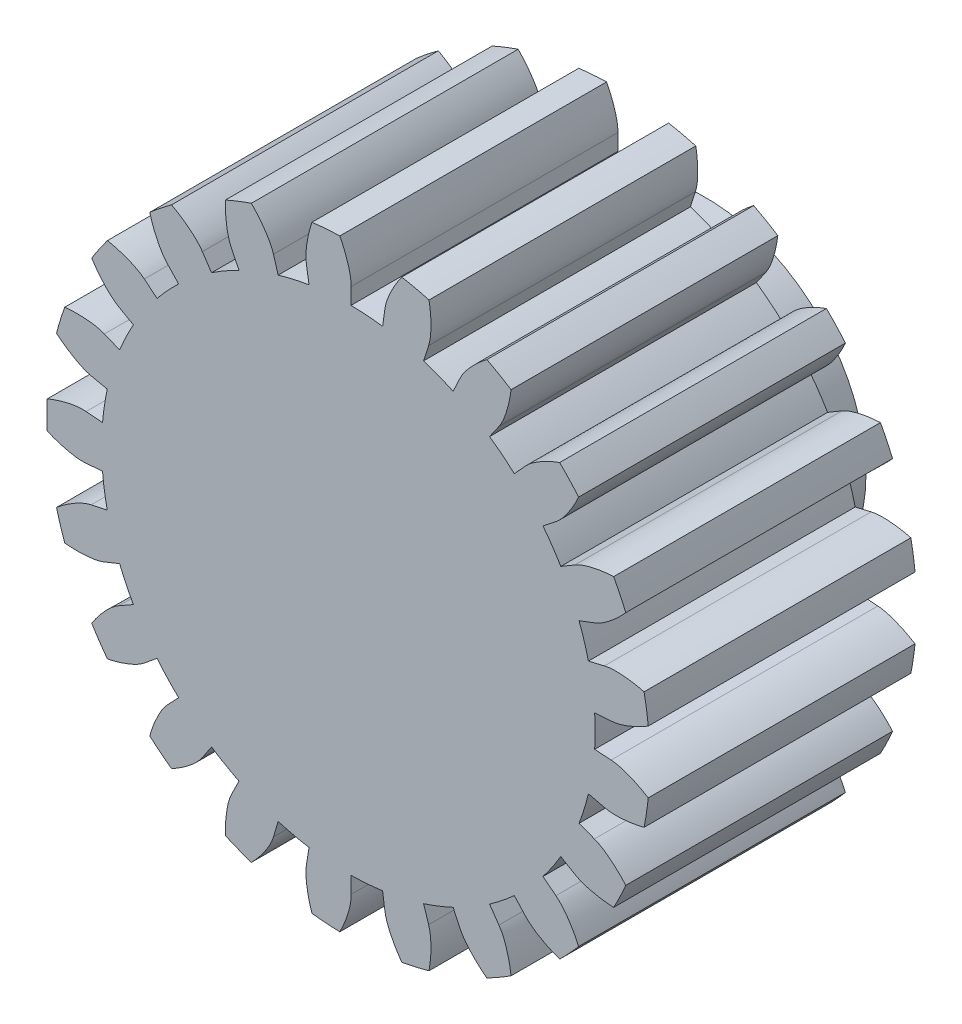
SolidWorks part; units mm, degrees
ref_plane "前视基准面" through (0, 0, 0) normal (0, 0, 1) x (1, 0, 0)
ref_plane "上视基准面" through (0, 0, 0) normal (0, 1, 0) x (1, 0, 0)
ref_plane "右视基准面" through (0, 0, 0) normal (1, 0, 0) x (0, 0, -1)
other "Configuration Table"
sketch "草图1" plane through (0, 0, 0) normal (0, 0, 1) x (1, 0, 0)
  line L0 (0, 0) -> (5.25, 0) construction
  line L1 (0, 0) -> (5.2353, 0.3923) construction
  line L2 (0, 0) -> (4.9232, 0.3169)
  line L3 (5.2353, 0.3923) -> (5.2353, -0.3923) construction
  line L4 (0, 0) -> (4.9232, -0.3169)
  circle A0 centre (0, 0) radius 5.75
  circle A1 centre (0, 0) radius 5.25 construction
  circle A2 centre (0, 0) radius 4.625
  circle A3 centre (0, 0) radius 4.9334 construction
  circle A4 centre (0, 0) radius 1.475
  spline S0 degree 4 poles (4.9232, 0.3169) (4.9607, 0.3193) (5.065, 0.3339) (5.2581, 0.3925) (5.555, 0.5296) (5.9082, 0.7653) (6.3141, 1.1289) (6.7208, 1.6221) (7.0851, 2.222) (7.4595, 3.0902) (7.6869, 4.0103) (7.7831, 4.9894) (7.7375, 6.1592) (7.5421, 7.3154) (7.1213, 8.6118) (6.437, 9.9622) (5.566, 11.1996) (4.5364, 12.3078) (3.3742, 13.2753) (2.1035, 14.0945) (0.7466, 14.7607) (-0.4976, 15.2081) (-1.5022, 15.4709) (-2.2418, 15.6171) (-2.7079, 15.6926) (-3.0798, 15.7435) (-3.4583, 15.7849) (-3.8273, 15.8169) (-4.1819, 15.8376) (-4.4716, 15.8494) (-4.8011, 15.8553) (-5.0151, 15.8558) (-5.3597, 15.8515) (-5.6291, 15.8407) (-5.9536, 15.8242) (-6.2447, 15.8018) (-6.5555, 15.7736) (-6.8526, 15.7397) (-7.0823, 15.71) (-7.2316, 15.6883) (-7.3069, 15.677) knots 0 0 0 0 0 0.005604 0.015718 0.02996 0.048734 0.068727 0.096889 0.125051 0.153212 0.209535 0.237696 0.271429 0.327752 0.384075 0.440398 0.496721 0.553044 0.609367 0.66569 0.722013 0.778336 0.806497 0.820578 0.834659 0.84874 0.86282 0.876901 0.890982 0.900036 0.909091 0.920455 0.931818 0.943182 0.954545 0.965909 0.977273 0.988636 1 1 1 1 1 construction
  spline S1 degree 4 poles (4.9232, 0.3169) (4.9607, 0.3193) (5.065, 0.3339) (5.2581, 0.3925) (5.555, 0.5296) (5.9082, 0.7653) (6.3141, 1.1289) (6.7208, 1.6221) (7.0851, 2.222) (7.4595, 3.0902) (7.6869, 4.0103) (7.7831, 4.9894) (7.7375, 6.1592) (7.5421, 7.3154) (7.1213, 8.6118) (6.437, 9.9622) (5.566, 11.1996) (4.5364, 12.3078) (3.3742, 13.2753) (2.1035, 14.0945) (0.7466, 14.7607) (-0.4976, 15.2081) (-1.5022, 15.4709) (-2.2418, 15.6171) (-2.7079, 15.6926) (-3.0798, 15.7435) (-3.4583, 15.7849) (-3.8273, 15.8169) (-4.1819, 15.8376) (-4.4716, 15.8494) (-4.7152, 15.8537) (-4.8263, 15.8548) (-4.8814, 15.855) knots 0 0 0 0 0 0.005604 0.015718 0.02996 0.048734 0.068727 0.096889 0.125051 0.153212 0.209535 0.237696 0.271429 0.327752 0.384075 0.440398 0.496721 0.553044 0.609367 0.66569 0.722013 0.778336 0.806497 0.820578 0.834659 0.84874 0.86282 0.876901 0.890982 0.900036 0.909091 0.909091 0.909091 0.909091 0.909091
  spline S2 degree 4 poles (4.9232, -0.3169) (4.9607, -0.3193) (5.065, -0.3339) (5.2581, -0.3925) (5.555, -0.5296) (5.9082, -0.7653) (6.3141, -1.1289) (6.7208, -1.6221) (7.0851, -2.222) (7.4595, -3.0902) (7.6869, -4.0103) (7.7831, -4.9894) (7.7375, -6.1592) (7.5421, -7.3154) (7.1213, -8.6118) (6.437, -9.9622) (5.566, -11.1996) (4.5364, -12.3078) (3.3742, -13.2753) (2.1035, -14.0945) (0.7466, -14.7607) (-0.4976, -15.2081) (-1.5022, -15.4709) (-2.2418, -15.6171) (-2.7079, -15.6926) (-3.0798, -15.7435) (-3.4583, -15.7849) (-3.8273, -15.8169) (-4.1819, -15.8376) (-4.4716, -15.8494) (-4.8011, -15.8553) (-5.0151, -15.8558) (-5.3597, -15.8515) (-5.6291, -15.8407) (-5.9536, -15.8242) (-6.2447, -15.8018) (-6.5555, -15.7736) (-6.8526, -15.7397) (-7.0823, -15.71) (-7.2316, -15.6883) (-7.3069, -15.677) knots 0 0 0 0 0 0.005604 0.015718 0.02996 0.048734 0.068727 0.096889 0.125051 0.153212 0.209535 0.237696 0.271429 0.327752 0.384075 0.440398 0.496721 0.553044 0.609367 0.66569 0.722013 0.778336 0.806497 0.820578 0.834659 0.84874 0.86282 0.876901 0.890982 0.900036 0.909091 0.920455 0.931818 0.943182 0.954545 0.965909 0.977273 0.988636 1 1 1 1 1 construction
  spline S3 degree 4 poles (4.9232, -0.3169) (4.9607, -0.3193) (5.065, -0.3339) (5.2581, -0.3925) (5.555, -0.5296) (5.9082, -0.7653) (6.3141, -1.1289) (6.7208, -1.6221) (7.0851, -2.222) (7.4595, -3.0902) (7.6869, -4.0103) (7.7831, -4.9894) (7.7375, -6.1592) (7.5421, -7.3154) (7.1213, -8.6118) (6.437, -9.9622) (5.566, -11.1996) (4.5364, -12.3078) (3.3742, -13.2753) (2.1035, -14.0945) (0.7466, -14.7607) (-0.4976, -15.2081) (-1.5022, -15.4709) (-2.2418, -15.6171) (-2.7079, -15.6926) (-3.0798, -15.7435) (-3.4583, -15.7849) (-3.8273, -15.8169) (-4.1819, -15.8376) (-4.4716, -15.8494) (-4.7152, -15.8537) (-4.8263, -15.8548) (-4.8814, -15.855) knots 0 0 0 0 0 0.005604 0.015718 0.02996 0.048734 0.068727 0.096889 0.125051 0.153212 0.209535 0.237696 0.271429 0.327752 0.384075 0.440398 0.496721 0.553044 0.609367 0.66569 0.722013 0.778336 0.806497 0.820578 0.834659 0.84874 0.86282 0.876901 0.890982 0.900036 0.909091 0.909091 0.909091 0.909091 0.909091
  point P15 (5.2353, 0)
  dimension "齿顶圆直径" = 11.5
  dimension "分度圆直径" = 10.5
  dimension "齿根圆直径" = 9.25
  dimension "基圆直径" = 9.8668
  dimension "内孔直径" = 2.95
  dimension "渐近线镜像线夹角" = 4.286
extrude "凸台-拉伸1" add sketch "草图1" along normal blind 5 contours A0 | A4
extrude "切除-拉伸1" cut sketch "草图1<3>" along normal through all contours A2 S3 A0 S1 region at (5.2601, 0, 0)
sketch "草图1<3>" plane through (0, 0, 0) normal (0, 0, 1) x (1, 0, 0) same geometry as "草图1"
pattern_circular "阵列(圆周)1" count 21 every 17.143 about axis through (0, 0, 5) along (0, 0, 1) of "切除-拉伸1"
sketch "草图2" plane through (0, 0, 5) normal (0, 0, 1) x (1, 0, 0)
  circle A0 centre (0, 0) radius 1.475
extrude "凸台-拉伸2" add sketch "草图2" against normal through all
sketch "草图3" plane through (0, 0, 0) normal (0, 0, -1) x (-1, 0, 0)
  line L7 (-1, 0.25) -> (1, 0.25)
  line L8 (-1, 0.25) -> (-1, -0.25)
  line L9 (-1, -0.25) -> (1, -0.25)
  line L10 (1, 0.25) -> (1, -0.25)
  line L11 (-0.25, 1) -> (0.25, 1)
  line L12 (-0.25, 1) -> (-0.25, -1)
  line L13 (-0.25, -1) -> (0.25, -1)
  line L14 (0.25, 1) -> (0.25, -1)
  circle A0 centre (0, 0) radius 2
  circle A1 centre (0, 0) radius 3
  point P13 (0, 1)
  point P14 (-0.25, 0)
  point P15 (-1, 0)
  point P16 (0, 0.25)
  dimension "D1" = 1
  dimension "D2" = 4
  dimension "D3" = 2
  dimension "D4" = 0.5
extrude "凸台-拉伸3" add sketch "草图3" along normal blind 1.7 contours A1 A0 | L9 L10 L7 L8 | L12 L13 L14 L11 region at (2.9151, 0, 0)
sketch "草图4" plane through (0, 0, 5) normal (0, 0, 1) x (1, 0, 0)
  line L0 (1, 1.118) -> (1, -1.118)
  circle A0 centre (0, 0) radius 1.5
  dimension "D1" = 3
  dimension "D2" = 1
sketch "草图5" plane through (0, 0, -1.7) normal (0, 0, -1) x (-1, 0, 0)
  circle A0 centre (0, 0) radius 2
  circle A1 centre (0, 0) radius 2 construction
extrude "切除-拉伸2" cut sketch "草图5" against normal blind 1
sketch "草图6" plane through (0, 0, 5) normal (0, 0, 1) x (1, 0, 0)
  circle A0 centre (0, 0) radius 5.65
  arc A1 (-2.3005, -5.2697) -> (-1.8979, -5.4277) centre (0, 0) ccw construction
  dimension "D1" = 0.1
extrude "切除-拉伸3" cut sketch "草图6" against normal through all flip side to cut
equation "\"m\"= 0.5'模数"
equation "\"z\"= 21'齿数"
equation "\"a\"= 20度'压力角"
equation "\"d\"= \"m\" * \"z\"'分度圆直径"
equation "\"da\"= ( \"z\" + 2 ) * \"m\"'齿顶圆直径"
equation "\"df\"= ( \"z\" - 2.5 ) * \"m\"'齿根圆直径"
equation "\"s\"= 0.5 * PI * \"m\"'分度圆齿厚"
equation "\"r\"= 0.38 * \"m\"'齿根圆角"
equation "\"B\"= 0.3 * \"d\"'齿厚"
equation "\"db\"= \"m\" * \"z\" * cos ( \"a\" )'基圆直径"
equation "\"rb\"= \"db\" / 2'基圆半径"
equation "\"齿顶圆直径@草图1\"= \"da\""
equation "\"分度圆直径@草图1\"= \"d\""
equation "\"齿根圆直径@草图1\"= \"df\""
equation "\"基圆直径@草图1\"= \"db\""
equation "\"渐近线镜像线夹角@草图1\"= 360 / 4 / \"z\""
equation "\"h\"= 5'齿轮厚度"
equation "\"ir\"= 2.95'内孔直径"
equation "\"内孔直径@草图1\"= \"ir\""
equation "\"齿轮厚@凸台-拉伸1\"= \"h\""
equation "\"齿轮夹角@阵列(圆周)1\"= 360 / \"z\""
equation "\"齿数@阵列(圆周)1\"= \"z\""
